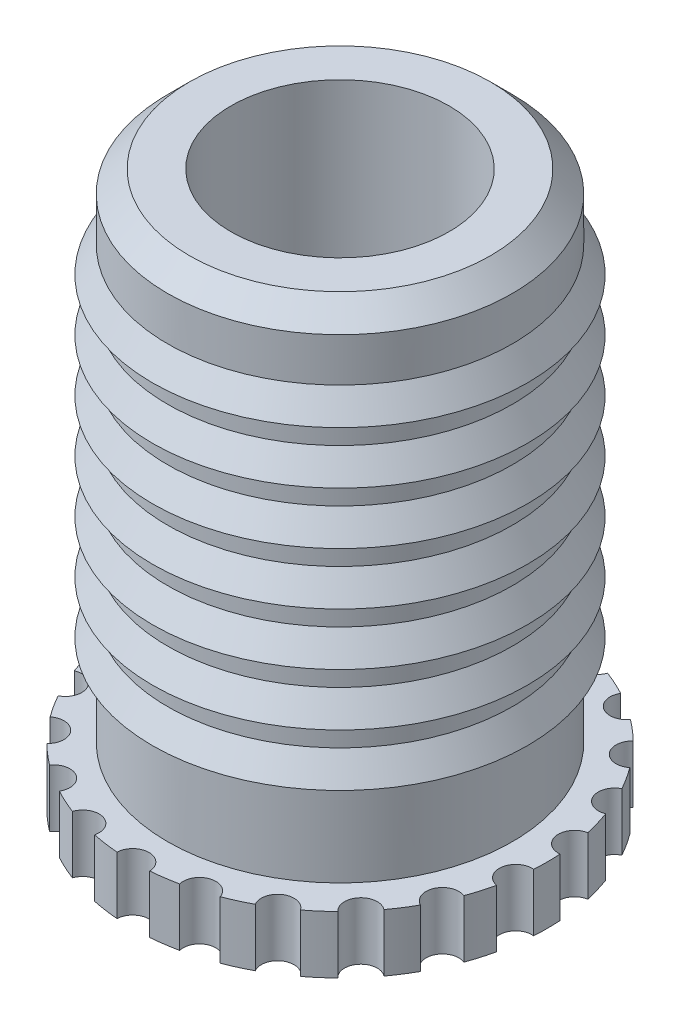
SolidWorks part; units mm, degrees
ref_plane "Front Plane" through (0, 0, 0) normal (0, 0, 1) x (1, 0, 0)
ref_plane "Top Plane" through (0, 0, 0) normal (0, 1, 0) x (1, 0, 0)
ref_plane "Right Plane" through (0, 0, 0) normal (1, 0, 0) x (0, 0, -1)
sketch "Sketch1" plane through (0, 0, 0) normal (0, 1, 0) x (1, 0, 0)
  circle A0 centre (0, 0) radius 2.5
  circle A1 centre (0, 0) radius 4.75
  dimension "D1" = 5
  dimension "D2" = 9.5
extrude "Boss-Extrude1" add sketch "Sketch1" along normal blind 1.32
sketch "Sketch2" plane through (0, 1.32, 0) normal (0, 1, 0) x (1, 0, 0)
  circle A0 centre (0, 0) radius 2.5 construction
  circle A1 centre (0, 0) radius 2.5
  circle A2 centre (0, 0) radius 3.95
  dimension "D1" = 7.9
extrude "Boss-Extrude2" add sketch "Sketch2" along normal blind 11.38
sketch "Sketch3" plane through (0, 0, 0) normal (0, 0, 1) x (1, 0, 0)
  line L0 (3.45, 11.2) -> (3.95, 11.2)
  line L2 (3.95, 1.32) -> (3.95, 12.7) construction
  line L3 (3.95, 11.2) -> (4.2964, 10.6)
  line L4 (4.2964, 10.6) -> (3.45, 10.6)
  line L6 (2.5, 12.7) -> (-2.5, 12.7) construction
  line L7 (3.45, 11.2) -> (3.45, 10.6)
  line L8 (0, 0) -> (0, 12.7) construction
  dimension "D1" = 0.6
  dimension "D2" = 0.5
  dimension "D3" = 60
  dimension "D4" = 1.5
revolve "Revolve1" add sketch "Sketch3" angle 360 about L8
pattern_linear "LPattern1" count 7 spacing 1.2 along (0, -1, 0) of "Revolve1"
chamfer "Chamfer1" distance 0.5 angle 45 1 edges at (0, 12.7, 3.95)
sketch "Sketch4" plane through (0, 0, 0) normal (0, -1, 0) x (1, 0, 0)
  circle A0 centre (0, 4.75) radius 0.375
  circle A1 centre (0, 0) radius 4.75 construction
  dimension "D1" = 0.75
extrude "Cut-Extrude1" cut sketch "Sketch4" against normal blind 2
pattern_circular "CirPattern1" count 22 over 360 about axis through (0, 0, 0) along (0, 1, 0) of "Cut-Extrude1"
